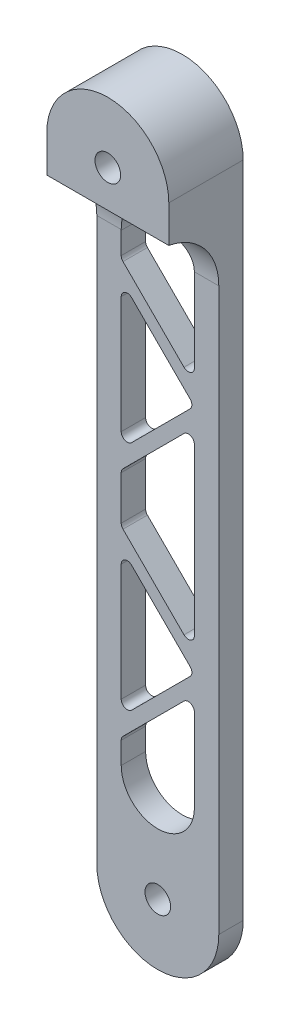
SolidWorks part; units mm, degrees
material "PLA"
ref_plane "Alzado" through (0, 0, 0) normal (0, 0, 1) x (1, 0, 0)
ref_plane "Planta" through (0, 0, 0) normal (0, 1, 0) x (1, 0, 0)
ref_plane "Vista lateral" through (0, 0, 0) normal (1, 0, 0) x (0, 0, -1)
sketch "Croquis1" plane through (0, 0, 0) normal (0, 0, 1) x (1, 0, 0)
  line L0 (0, 54) -> (0, -54) construction
  line L1 (10, 54) -> (10, -54)
  line L2 (-10, 54) -> (-10, -54)
  line L3 (0, 38) -> (0, -38) construction
  line L4 (6, 38) -> (6, -38)
  line L5 (-6, 38) -> (-6, -38)
  line L6 (-10, -47.95) -> (10, -47.95)
  line L7 (0, 51.9) -> (0, 44) construction
  line L8 (-10, 47.95) -> (10, 47.95)
  line L9 (0, -51.9) -> (0, -44) construction
  line L10 (-10, 0) -> (10, 0) construction
  line L11 (6, -19) -> (-6, -31)
  line L12 (-6, -34) -> (6, -22)
  line L13 (0, -38) -> (0, 0) construction
  line L14 (-6, -19) -> (6, -19) construction
  line L15 (-6, -4) -> (6, -16)
  line L16 (6, -19) -> (-6, -7)
  line L17 (-6, 4) -> (6, 16)
  line L18 (6, 19) -> (-6, 7)
  line L19 (6, 19) -> (-6, 31)
  line L20 (-6, 34) -> (6, 22)
  arc A0 (10, 54) -> (-10, 54) centre (0, 54) ccw
  arc A1 (-10, -54) -> (10, -54) centre (0, -54) ccw
  circle A2 centre (0, 54) radius 2.1
  circle A3 centre (0, -54) radius 2.1
  arc A4 (6, 38) -> (-6, 38) centre (0, 38) ccw
  arc A5 (-6, -38) -> (6, -38) centre (0, -38) ccw
  point P2 (0, 0)
  point P14 (0, 0)
  point P23 (0, 47.95)
  point P28 (0, -47.95)
  point P39 (0, -19)
  dimension "D1" = 4.2
  dimension "D2" = 20
  dimension "D3" = 108
  dimension "D4" = 4
  dimension "D5" = 16
  dimension "D6" = 135
  dimension "D7" = 3
extrude "Saliente-Extruir1" add sketch "Croquis1" along normal blind 4 contours L1 A0 L2 L8 A2 | L2 A1 L1 L8 A5 L5 A4 L4 A3 | L5 L12 L4 L11 | L16 L4 L15 L5 | L4 L18 L5 L17 | L20 L5 L19 L4 | L2 A1 L1 A0 | A3 | L5 A5 L4 A4 | A2 region at (9.7436, 50.975, 0) region at (9.0204, 0, 0) region at (0, 26.5, 0) region at (0, 11.5, 0) region at (0, -11.5, 0) region at (0, -26.5, 0)
extrude "Saliente-Extruir3" add sketch "Croquis1<6>" along normal blind 12.2 contours L1 A0 L2 L8 A2 region at (9.7436, 50.975, 0)
sketch "Croquis1<6>" plane through (0, 0, 0) normal (0, 0, 1) x (1, 0, 0) same geometry as "Croquis1"
fillet "Redondeo1" radius 10 1 edges at (0, 47.95, 4)
fillet "Redondeo2" radius 1 14 edges at (-6, 34, 2) (6, 22, 2) (6, 19, 2) (-6, 31, 2) (-6, 7, 2) (6, 16, 2) (-6, -4, 2) (-6, 4, 2) (6, -16, 2) (6, -19, 2) (6, -22, 2) (-6, -31, 2) (-6, -7, 2) (-6, -34, 2)
